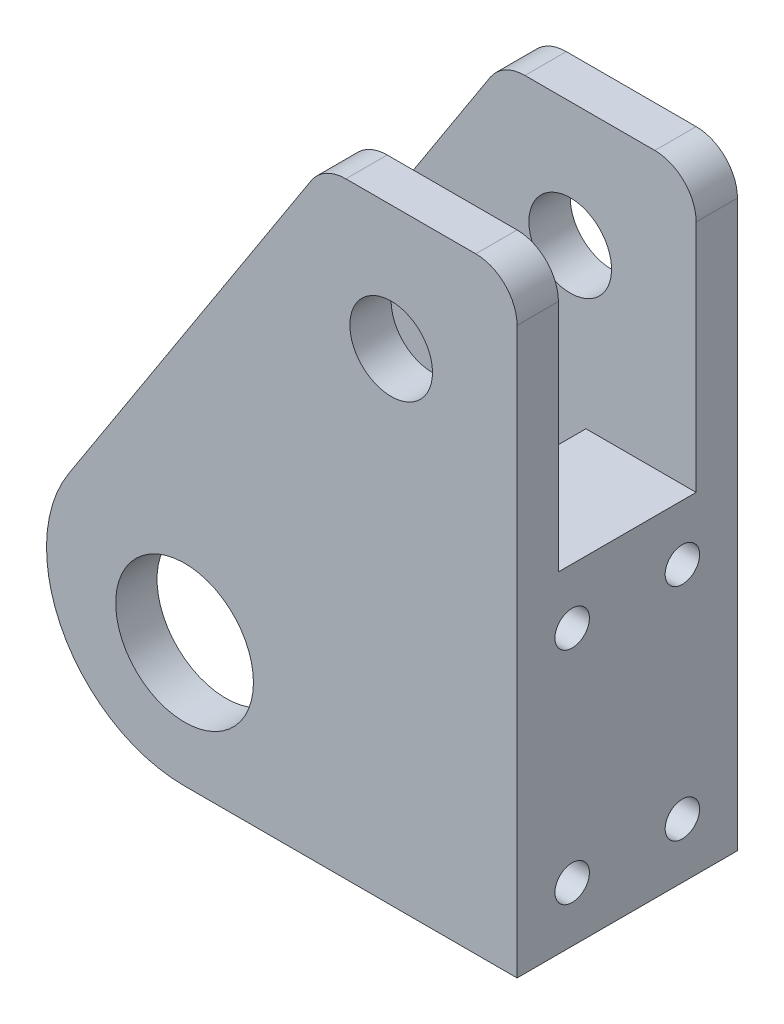
SolidWorks part; units mm, degrees
ref_plane "前视基准面" through (0, 0, 0) normal (0, 0, 1) x (1, 0, 0)
ref_plane "上视基准面" through (0, 0, 0) normal (0, 1, 0) x (1, 0, 0)
ref_plane "右视基准面" through (0, 0, 0) normal (1, 0, 0) x (0, 0, -1)
sketch "草图1" plane through (0, 0, 0) normal (0, 0, 1) x (1, 0, 0)
  line L0 (-31.6676, -19.7128) -> (-15.2145, -22.1776)
  line L1 (-14.3627, -23.1665) -> (-14.3627, -25.0152)
  line L2 (-14.3627, -25.0152) -> (39.5973, -25.0152)
  line L3 (39.5973, -25.0152) -> (39.5973, -20.0152)
  line L4 (39.5973, -20.0152) -> (-6.3993, -20.0152)
  line L5 (-6.3993, -20.0152) -> (-6.3993, 14.685)
  line L6 (-23.0573, 19.8462) -> (-38.645, -4.2544)
  line L7 (-14.3627, -23.1665) -> (-14.3627, -22.3052)
  line L8 (-15.2145, -22.1776) -> (-14.3627, -22.3052)
  circle A0 centre (-30.4398, -11.0045) radius 3
  circle A1 centre (-15.4402, 14.9762) radius 3
  arc A3 (-6.3993, 14.685) -> (-6.428, 15.7523) centre (-15.4402, 14.9762) ccw
  arc A4 (-6.4414, 15.8482) -> (-6.428, 15.7523) centre (-4.4548, 16.0786) ccw
  arc A5 (-6.4414, 15.8482) -> (-23.0573, 19.8462) centre (-15.4402, 14.9762) ccw
  arc A6 (-38.645, -4.2544) -> (-31.6676, -19.7128) centre (-30.1727, -9.7341) ccw
extrude "凸台-拉伸1" add sketch "草图1" along normal blind 2
sketch "草图2" plane through (0, -25.0152, 0) normal (0, -1, 0) x (1, 0, 0)
  line L0 (39.5973, -13) -> (39.5973, 2)
  line L1 (39.5973, 2) -> (-14.3627, 2)
  line L2 (-14.3627, 2) -> (-14.3627, -13)
  line L3 (-14.3627, -13) -> (39.5973, -13)
  line L4 (3.3678, -1.25) -> (-1.4912, -1.25)
  line L5 (18.7088, -1.25) -> (10.3499, -1.25)
  line L6 (18.7088, -9.75) -> (18.7088, -1.25)
  line L7 (10.3499, -9.75) -> (18.7088, -9.75)
  line L8 (-1.4912, -9.75) -> (3.3678, -9.75)
  line L9 (-1.4912, -1.25) -> (-1.4912, -9.75)
  arc A0 (10.3499, -1.25) -> (3.3678, -1.25) centre (6.8588, -5.5) ccw
  arc A1 (3.3678, -9.75) -> (10.3499, -9.75) centre (6.8588, -5.5) ccw
  circle A2 centre (26.6373, -5.5) radius 1.6
  circle A3 centre (-9.3627, -5.5) radius 1.6
  circle A4 centre (-3.1412, -5.5) radius 1
  circle A5 centre (20.3588, -5.5) radius 1
extrude "凸台-拉伸2" add sketch "草图2" against normal blind 2
pattern_linear "阵列(线性)1" count 2 spacing 13 along (0, 0, -1) of "凸台-拉伸1"
fillet "圆角1" radius 1 1 edges at (-14.3627, -22.3052, 1)
sketch "草图4" plane through (0, 0, 2) normal (0, 0, 1) x (1, 0, 0)
  line L0 (-20.3597, 24.0171) -> (-48.8388, -20.0152)
  line L1 (-48.8388, -20.0152) -> (-6.2993, -20.0152)
  line L2 (-20.3597, 24.0171) -> (-6.2993, 24.0171)
  line L3 (-6.2993, 24.0171) -> (-6.2993, -20.0152)
  line L5 (-6.3993, -20.0152) -> (-6.3993, 14.685) construction
  line L6 (-23.0573, 19.8462) -> (-38.645, -4.2544) construction
  line L8 (39.5973, -20.0152) -> (-6.3993, -20.0152) construction
  arc A0 (-6.4414, 15.8482) -> (-23.0573, 19.8462) centre (-15.4402, 14.9762) ccw construction
  circle A1 centre (-15.4402, 14.9762) radius 3
  circle A2 centre (-30.4398, -11.0045) radius 3
  dimension "D1" = 6
  dimension "D2" = 6
  dimension "D3" = 0.1
extrude "凸台-拉伸3" add sketch "草图4" against normal blind 16
sketch "草图5" plane through (0, 0, 2) normal (0, 0, 1) x (1, 0, 0)
  line L0 (-48.8388, -20.0152) -> (-29.6489, -20.0152) construction
  line L1 (-32, -20.0152) -> (39.5973, -20.0152)
  line L2 (-32, -20.0152) -> (-32, -30.0152)
  line L3 (-32, -30.0152) -> (39.5973, -30.0152)
  line L4 (39.5973, -20.0152) -> (39.5973, -30.0152)
  line L5 (39.5973, -25.0152) -> (39.5973, -20.0152) construction
  dimension "D1" = 10
  dimension "D2" = 32
extrude "切除-拉伸1" cut sketch "草图5" against normal up to surface (15 mm away) up to face at (-0.0729, -22.1803, -13)
sketch "草图6" plane through (0, 0, 2) normal (0, 0, 1) x (1, 0, 0)
  circle A0 centre (-30.4398, -11.0045) radius 5
  dimension "D1" = 10
extrude "切除-拉伸2" cut sketch "草图6" against normal blind 3
sketch "草图7" plane through (0, 0, -14) normal (0, 0, -1) x (-1, 0, 0)
  circle A0 centre (30.4398, -11.0045) radius 5
  dimension "D1" = 10
extrude "切除-拉伸3" cut sketch "草图7" against normal blind 3
fillet "圆角2" radius 10 1 edges at (-48.8388, -20.0152, -6)
sketch "草图8" plane through (-25.3069, 16.368, 0) normal (-0.8397, 0.5431, 0) x (0, 0, 1)
  line L0 (-13, 4.1423) -> (-13, 4.2374) construction
  line L1 (-13, 4.2374) -> (-11, 4.2374)
  line L2 (-13, 4.2374) -> (-13, 4.1423)
  line L3 (-13, 4.1423) -> (-11, 4.1423)
  line L4 (-11, 4.2374) -> (-11, 4.1423)
  line L5 (-11, 4.2374) -> (-13, 4.2374) construction
  line L6 (-11, 4.1423) -> (-13, 4.1423) construction
  line L7 (-11, 4.2374) -> (-11, 4.1423) construction
  line L9 (0, 4.2374) -> (2, 4.2374)
  line L10 (0, 4.2374) -> (0, 4.1423)
  line L11 (0, 4.1423) -> (2, 4.1423)
  line L12 (2, 4.2374) -> (2, 4.1423)
extrude "凸台-拉伸5" add sketch "草图8" along normal blind 0.002
sketch "草图9" plane through (0, 0, 2) normal (0, 0, 1) x (1, 0, 0)
  line L0 (-23.0057, 19.926) -> (-23.0573, 19.8462)
  line L1 (-23.0057, 19.926) -> (-23.8453, 20.4691)
  line L2 (-23.0073, 19.9271) -> (-23.0057, 19.926) construction
  line L3 (-23.0573, 19.8462) -> (-23.897, 20.3892)
  line L4 (-23.059, 19.8472) -> (-23.0573, 19.8462) construction
  line L5 (-23.8453, 20.4691) -> (-23.897, 20.3892)
  dimension "D1" = 1
extrude "切除-拉伸4" cut sketch "草图9" against normal up to surface (16 mm away) up to face at (-35.4398, -11.0045, -14)
fillet "圆角3" radius 3 2 edges at (-20.3597, 24.0171, -6) (-6.2993, 24.0171, -6)
sketch "草图11" plane through (0, 24.0171, 0) normal (0, 1, 0) x (1, 0, 0)
  line L0 (-6.2993, 6) -> (-71.9064, 6) construction
  line L1 (-6.2993, 14) -> (-6.2993, -2) construction
  line L2 (-21.2462, 14) -> (-38.8584, 14) construction
  line L3 (-14.2993, 1) -> (-50.5232, 1)
  line L4 (-14.2993, 1) -> (-14.2993, 11)
  line L5 (-14.2993, 11) -> (-50.5232, 11)
  line L6 (-50.5232, 1) -> (-50.5232, 11)
  line L7 (-14.2993, 1) -> (-50.5232, 11) construction
  line L8 (-14.2993, 11) -> (-50.5232, 1) construction
  point P4 (-32.4113, 6)
  dimension "D1" = 3
  dimension "D2" = 8
extrude "切除-拉伸5" cut sketch "草图11" against normal up to surface (44.0322 mm away) up to face at (-18.3805, -20.0152, -6)
sketch "草图14" plane through (-14.2993, 0, 0) normal (-1, 0, 0) x (0, 0, 1)
  line L0 (-1, -20.0152) -> (-1, 12.2016) construction
  line L1 (-11, 24.0171) -> (-1, 24.0171)
  line L2 (-11, 24.0171) -> (-11, 4.0171)
  line L3 (-11, 4.0171) -> (-1, 4.0171)
  line L4 (-1, 24.0171) -> (-1, 4.0171)
  dimension "D1" = 20
extrude "切除-拉伸6" cut sketch "草图14" against normal up to surface (8 mm away) up to face at (-6.2993, 0.5009, -6)
hole_wizard "M3 螺纹孔1" positions "草图17" profile "草图18" tap size "M3" standard "GB"
sketch "草图17" plane through (-6.2993, 0, 0) normal (1, 0, 0) x (0, 0, -1)
  line L0 (14, -20.0152) -> (-2, -20.0152) construction
  line L1 (-2, -20.0152) -> (-2, 21.0171) construction
  line L2 (14, -20.0152) -> (14, 21.0171) construction
  point P0 (2, -0.0152)
  point P2 (10, -0.0152)
  point P4 (2, -16.0152)
  point P6 (10, -16.0152)
  dimension "D1" = 4
  dimension "D2" = 4
  dimension "D3" = 4
  dimension "D4" = 4
  dimension "D5" = 4
  dimension "D6" = 4
  dimension "D7" = 16
  dimension "D8" = 16
sketch "草图18" plane through (-6.2993, -0.0152, -2) normal (0, 1, 0) x (0, 0, -1)
  line L0 (0, 0) -> (0, 8.2511)
  line L1 (0, 8.2511) -> (1.25, 7.5)
  line L2 (1.25, 7.5) -> (1.25, 0)
  line L5 (1.25, 0) -> (0, 0)
  line L10 (0, 8.2511) -> (-1.25, 7.5) construction
  line L11 (0, -6.35) -> (0, 107.95) construction
  dimension "螺纹孔钻头直径" = 2.5
  dimension "螺纹孔钻头深度" = 7.5
  dimension "导头角度" = 118
cosmetic thread "孔螺蚊线1" parameters "D1"=6, "D2"=3
cosmetic thread "孔螺蚊线2" parameters "D1"=6, "D2"=3
cosmetic thread "孔螺蚊线3" parameters "D1"=6, "D2"=3
cosmetic thread "孔螺蚊线4" parameters "D1"=6, "D2"=3
